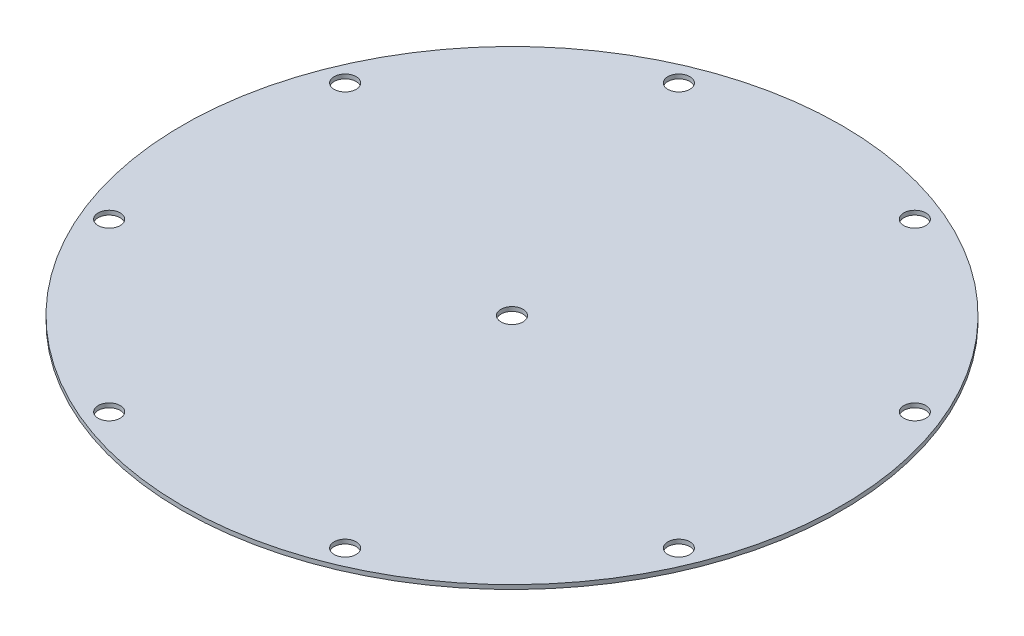
SolidWorks part; units mm, degrees
material "6061-T6 (SS)"
ref_plane "Front Plane" through (0, 0, 0) normal (0, 0, 1) x (1, 0, 0)
ref_plane "Top Plane" through (0, 0, 0) normal (0, 1, 0) x (1, 0, 0)
ref_plane "Right Plane" through (0, 0, 0) normal (1, 0, 0) x (0, 0, -1)
sketch "Sketch2" plane through (0, 0, 0) normal (1, 0, 0) x (0, 0, -1)
  line L0 (0, 0) -> (-77.55, 0)
  line L1 (-77.55, 0) -> (-77.55, 1)
  line L2 (-77.55, 1) -> (0, 1)
  line L5 (0, 1) -> (0, 0)
  dimension "D1" = 77.55
  dimension "D2" = 1
ref_axis "Axis1" through (0, -0.05, 0) along (0, 1, 0)
revolve "Revolve1" add sketch "Sketch2" angle 360 about axis through (0, -0.05, 0) along (0, 1, 0)
hole_wizard "#6 (0.204) Diameter Hole1" positions "Sketch6" profile "Sketch7" hole size "#6" standard "ANSI Inch" end condition through all
sketch "Sketch6" plane through (0, 1, 0) normal (0, 1, 0) x (1, 0, 0)
  line L0 (0, 0) -> (-53.438, 129.0108) construction
  line L2 (0, 0) -> (0, 109.0908) construction
  point P0 (-27.7637, 67.0275)
  dimension "D1" = 22.5
  dimension "D2" = 72.55
sketch "Sketch7" plane through (-27.7637, 1, -67.0275) normal (1, 0, 0) x (0, 0, 1)
  line L0 (0, 0) -> (0, 1)
  line L1 (0, 1) -> (2.5908, 1)
  line L2 (2.5908, 1) -> (2.5908, 0)
  line L5 (2.5908, 0) -> (0, 0)
  line L11 (0, -6.35) -> (0, 107.95) construction
  dimension "Thru Hole Dia." = 5.1816
  dimension "Thru Hole Depth" = 1
pattern_circular "CirPattern3" count 8 over 360 about axis through (0, -0.05, 0) along (0, 1, 0) of "#6 (0.204) Diameter Hole1"
hole_wizard "#6 (0.204) Diameter Hole2" positions "Sketch8" profile "Sketch9" hole size "#6" standard "ANSI Inch" end condition through all
sketch "Sketch8" plane through (0, 1, 0) normal (0, 1, 0) x (1, 0, 0)
  line L0 (0, 0) -> (106.3094, -1.7118) construction
  point P7 (0, 0)
sketch "Sketch9" plane through (0, 1, 0) normal (1, 0, 0) x (0, 0, 1)
  line L0 (0, 0) -> (0, 1)
  line L1 (0, 1) -> (2.5908, 1)
  line L2 (2.5908, 1) -> (2.5908, 0)
  line L5 (2.5908, 0) -> (0, 0)
  line L11 (0, -6.35) -> (0, 107.95) construction
  dimension "Thru Hole Dia." = 5.1816
  dimension "Thru Hole Depth" = 1
equation "\"TubeDiameter\" = 6.500in"
equation "\"D1@Sketch2\"=\"TubeDiameter\"/2-5mm"
equation "\"D2@Sketch6\"=\"TubeDiameter\"/2-10mm"
